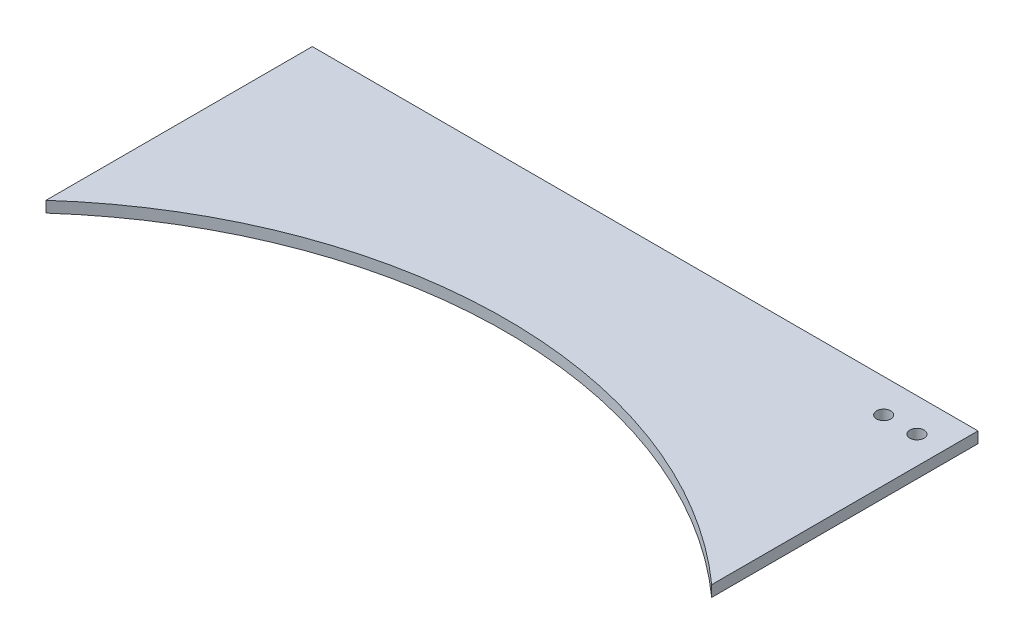
SolidWorks part; units mm, degrees
ref_plane "Front Plane" through (0, 0, 0) normal (0, 0, 1) x (1, 0, 0)
ref_plane "Top Plane" through (0, 0, 0) normal (0, 1, 0) x (1, 0, 0)
ref_plane "Right Plane" through (0, 0, 0) normal (1, 0, 0) x (0, 0, -1)
sketch "Sketch1" plane through (0, 0, 0) normal (0, 1, 0) x (1, 0, 0)
  line L0 (0, 0) -> (0, 76.2)
  line L1 (0, 76.2) -> (190.5, 76.2)
  line L2 (190.5, 76.2) -> (190.5, 0)
  arc A0 (0, 0) -> (190.5, 0) centre (95.25, -106.4927) cw
  dimension "D3" = 142.875
  dimension "D1" = 76.2
  dimension "D2" = 190.5
extrude "Boss-Extrude1" add sketch "Sketch1" along normal blind 3.175
sketch "Sketch3" plane through (0, 0, 0) normal (0, -1, 0) x (1, 0, 0)
  circle A16 centre (182.5625, -66.675) radius 2.032 construction
  circle A17 centre (173.0375, -66.675) radius 2.032 construction
  circle A18 centre (182.5625, -66.675) radius 2.032
  circle A19 centre (173.0375, -66.675) radius 2.032
extrude "Cut-Extrude1" cut sketch "Sketch3" against normal through all
